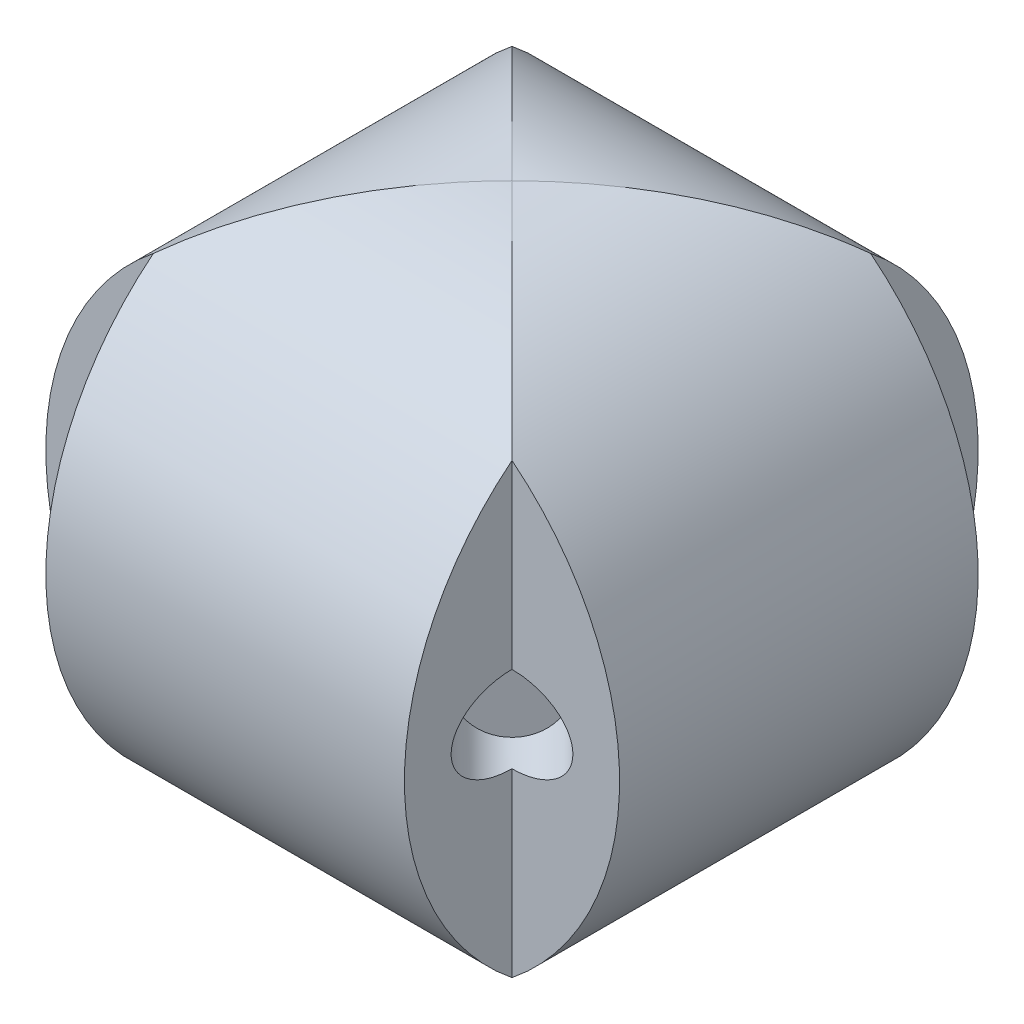
SolidWorks part; units mm, degrees
material "热轧圆钢 45"
ref_plane "前视基准面" through (0, 0, 0) normal (0, 0, 1) x (1, 0, 0)
ref_plane "上视基准面" through (0, 0, 0) normal (0, 1, 0) x (1, 0, 0)
ref_plane "右视基准面" through (0, 0, 0) normal (1, 0, 0) x (0, 0, -1)
sketch "草图3" plane through (0, 0, 0) normal (1, 0, 0) x (0, 0, -1)
  line L0 (0, 40) -> (0, -40)
  arc A0 (0, -40) -> (0, 40) centre (0, 0) ccw
  dimension "D1" = 80
revolve "旋转1" add sketch "草图3" angle 360 about L0
sketch "草图4" plane through (0, 0, 0) normal (0, 0, 1) x (1, 0, 0)
  line L0 (-25, 50) -> (25, 50)
  line L1 (25, 50) -> (12.5, 20)
  line L2 (12.5, 20) -> (-12.5, 20)
  line L3 (-12.5, 20) -> (-25, 50)
  line L4 (0, 50.5448) -> (0, -50.4322) construction
  line L5 (-55.2479, 0) -> (81.1192, 0) construction
  dimension "D1" = 50
  dimension "D2" = 25
  dimension "D3" = 25
  dimension "D4" = 12.5
  dimension "D5" = 20
  dimension "D6" = 50
revolve "切除-旋转3" cut sketch "草图4" angle 360 about L5
sketch "草图5" plane through (0, 0, 0) normal (0, 1, 0) x (1, 0, 0)
  line L0 (-48.3452, 0) -> (63.4223, 0) construction
  line L1 (0, 44.0023) -> (0, -58.5878) construction
  line L2 (-50, 25) -> (-50, -25)
  line L3 (-50, -25) -> (-20, -12.5)
  line L4 (-20, -12.5) -> (-20, 12.5)
  line L5 (-20, 12.5) -> (-50, 25)
  dimension "D1" = 50
  dimension "D2" = 20
  dimension "D3" = 50
  dimension "D4" = 25
  dimension "D5" = 25
  dimension "D6" = 12.5
revolve "切除-旋转4" cut sketch "草图5" angle 360 about L1
sketch "草图6" plane through (0, 0, 0) normal (0, 1, 0) x (1, 0, 0)
  line L0 (-20, 12.5) -> (-20, -12.5) construction
  line L5 (-20, 20) -> (20, 20)
  line L6 (-20, 20) -> (-20, -20)
  line L7 (-20, -20) -> (20, -20)
  line L8 (20, 20) -> (20, -20)
  line L9 (12.5, 20) -> (-12.5, 20) construction
  line L10 (20, -12.5) -> (20, 12.5) construction
  line L11 (-12.5, -20) -> (12.5, -20) construction
  line L13 (-59.8752, 45.8237) -> (49.8255, 45.8237)
  line L14 (-59.8752, 45.8237) -> (-59.8752, -56.259)
  line L15 (-59.8752, -56.259) -> (49.8255, -56.259)
  line L16 (49.8255, 45.8237) -> (49.8255, -56.259)
extrude "切除-拉伸2" cut sketch "草图6" against normal through all both and the other way through all
ref_plane "基准面1" through (0, 29.8048, 0) normal (0, 1, 0) x (1, 0, 0)
sketch "草图7" plane through (0, 29.8048, 0) normal (0, 1, 0) x (1, 0, 0)
  line L0 (-12.5, 20) -> (-12.5, 12.5)
  line L1 (-12.5, 12.5) -> (-20, 12.5)
  line L2 (-20, 12.5) -> (-20, 22.4002)
  line L3 (-20, 22.4002) -> (-12.5, 22.4002)
  line L4 (-12.5, 22.4002) -> (-12.5, 20)
  line L5 (12.5, 12.5) -> (22.9302, 12.5)
  line L6 (22.9302, 12.5) -> (22.9302, 22.4002)
  line L7 (22.9302, 22.4002) -> (12.5, 22.4002)
  line L8 (12.5, 22.4002) -> (12.5, 12.5)
  line L9 (-12.5, -12.5) -> (-12.5, -22.2886)
  line L10 (-12.5, -22.2886) -> (-23.265, -21.6749)
  line L11 (-23.265, -21.6749) -> (-21.8702, -13.8641)
  line L12 (-21.8702, -13.8641) -> (-20, -12.5)
  line L13 (-20, -12.5) -> (-12.5, -12.5)
  line L14 (12.5, -12.5) -> (12.5, -20)
  line L15 (-12.5, -20) -> (12.5, -20) construction
  line L16 (12.5, -20) -> (16.2911, -21.9818)
  line L17 (16.2911, -21.9818) -> (20, -20)
  line L18 (20, -20) -> (23.265, -15.6818)
  line L19 (23.265, -15.6818) -> (21.6325, -12.6266)
  line L20 (21.6325, -12.6266) -> (20, -12.5)
  line L21 (20, -12.5) -> (12.5, -12.5)
extrude "切除-拉伸3" cut sketch "草图7" against normal through all
ref_plane "基准面2" through (0, 0, 0) normal (0.7071, 0, -0.7071) x (-0.7071, 0, -0.7071)
ref_plane "基准面3" through (0, 0, 0) normal (-0.7071, 0, -0.7071) x (-0.7071, 0, 0.7071)
ref_plane "基准面4" through (0, 0, 0) normal (0.7071, 0, 0.7071) x (0.7071, 0, -0.7071)
ref_plane "基准面5" through (0, 0, 0) normal (-0.7071, 0, 0.7071) x (0.7071, 0, 0.7071)
sketch "草图8" plane through (0, 0, 0) normal (0.7071, 0, -0.7071) x (-0.7071, 0, -0.7071)
  line L0 (-25.0843, 0) -> (40.8892, 0) construction
  line L2 (15, 0) -> (35.2617, 0)
  line L3 (15, 0) -> (15, 3)
  line L4 (15, 3) -> (35.2617, 3)
  line L5 (35.2617, 0) -> (35.2617, 3)
  dimension "D1" = 3
  dimension "D2" = 15
revolve "切除-旋转5" cut sketch "草图8" angle 360 about L0
sketch "草图9" plane through (0, 0, 0) normal (-0.7071, 0, -0.7071) x (-0.7071, 0, 0.7071)
  line L0 (-24.9645, 0) -> (38.3149, 0) construction
  line L2 (-15, 0) -> (-35.8005, 0)
  line L3 (-15, 0) -> (-15, 3)
  line L4 (-15, 3) -> (-35.8005, 3)
  line L5 (-35.8005, 0) -> (-35.8005, 3)
  dimension "D1" = 3
  dimension "D2" = 15
revolve "切除-旋转6" cut sketch "草图9" angle 360 about L0
sketch "草图11" plane through (0, 0, 0) normal (0.7071, 0, 0.7071) x (0.7071, 0, -0.7071)
  line L0 (-26.7606, 0) -> (32.1486, 0) construction
  line L2 (-15, 0) -> (-35.3814, 0)
  line L3 (-15, 0) -> (-15, 3)
  line L4 (-15, 3) -> (-35.3814, 3)
  line L5 (-35.3814, 0) -> (-35.3814, 3)
  dimension "D1" = 3
  dimension "D2" = 15
revolve "切除-旋转10" cut sketch "草图11" angle 360 about L0
sketch "草图12" plane through (0, 0, 0) normal (-0.7071, 0, 0.7071) x (0.7071, 0, 0.7071)
  line L0 (0, 0) -> (37.357, 0) construction
  line L2 (15, 0) -> (36.3991, 0)
  line L3 (15, 0) -> (15, 3)
  line L4 (15, 3) -> (36.3991, 3)
  line L5 (36.3991, 0) -> (36.3991, 3)
  dimension "D1" = 3
  dimension "D2" = 15
revolve "切除-旋转11" cut sketch "草图12" angle 360 about L0
